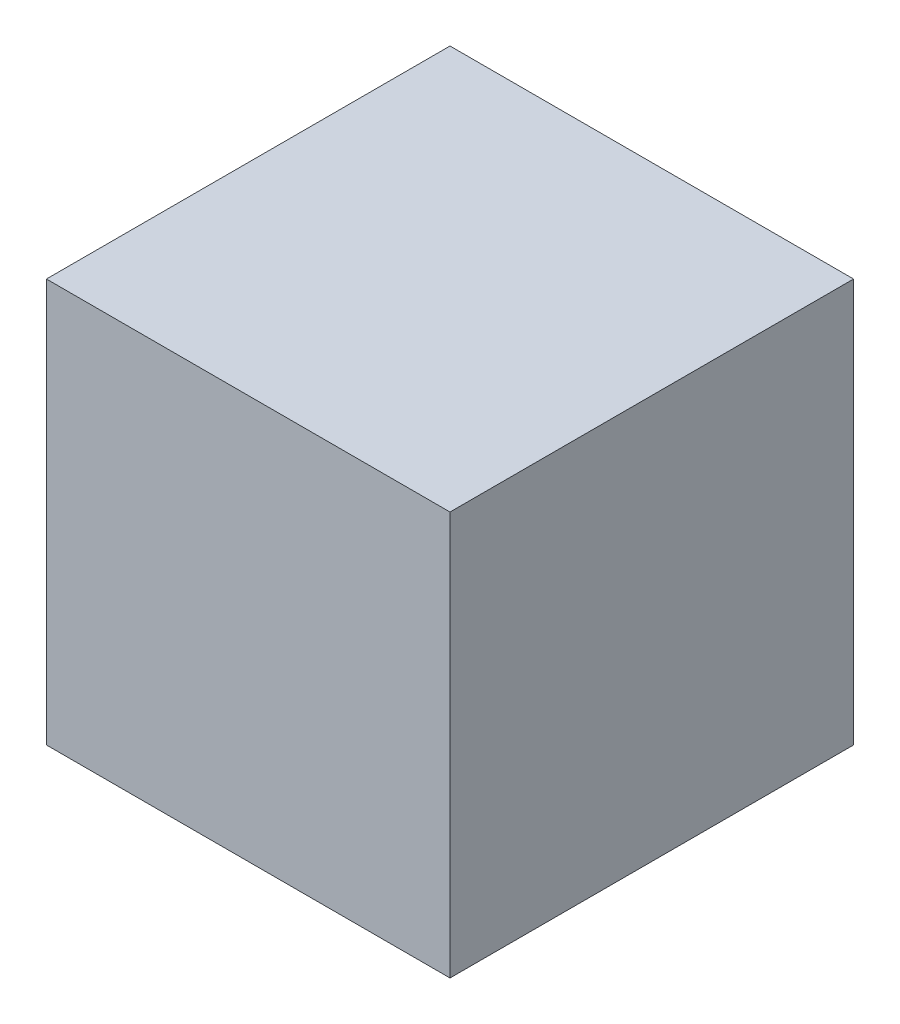
SolidWorks part; units mm, degrees
ref_plane "Plan de face" through (0, 0, 0) normal (0, 0, 1) x (1, 0, 0)
ref_plane "Plan de dessus" through (0, 0, 0) normal (0, 1, 0) x (1, 0, 0)
ref_plane "Plan de droite" through (0, 0, 0) normal (1, 0, 0) x (0, 0, -1)
other "Centre de masse"
sketch "Esquisse1" plane through (0, 0, 0) normal (0, 0, 1) x (1, 0, 0)
  line L1 (-25, 25) -> (25, 25)
  line L2 (-25, 25) -> (-25, -25)
  line L3 (-25, -25) -> (25, -25)
  line L4 (25, 25) -> (25, -25)
  line L5 (-25, 25) -> (25, -25) construction
  line L6 (-25, -25) -> (25, 25) construction
  point P0 (0, 0)
  dimension "D1" = 50
  dimension "D2" = 50
extrude "Boss.-Extru.1" add sketch "Esquisse1" along normal blind 25 and the other way blind 25
ref_point "Point1"
sketch "Esquisse2" plane through (-25, 0, 0) normal (-1, 0, 0) x (0, 0, 1)
  line L0 (-25, -25) -> (25, -25) construction
  line L1 (25, 25) -> (25, -25) construction
  point P0 (0, -25)
  dimension "D1" = 25
